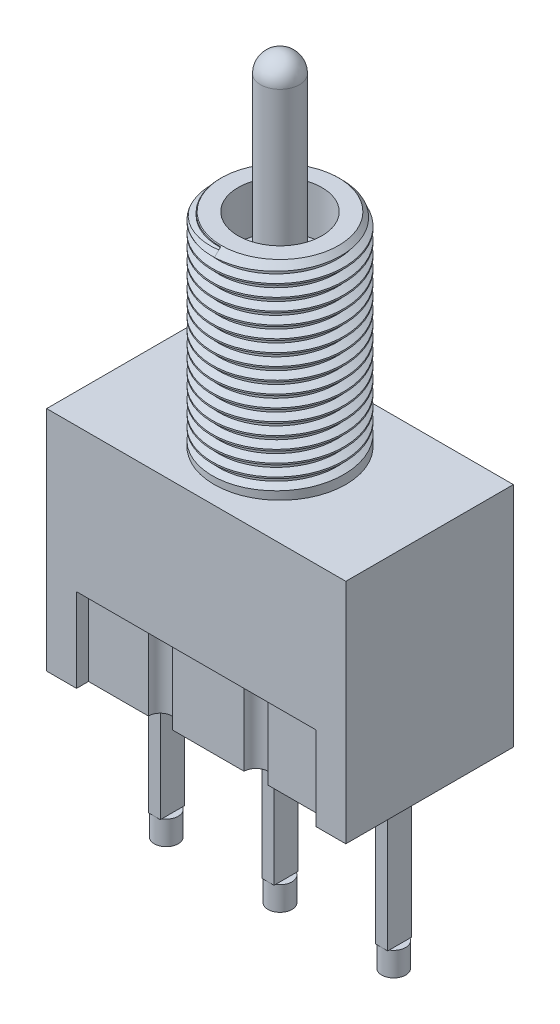
SolidWorks part; units mm, degrees
ref_plane "Front" through (0, 0, 0) normal (0, 0, 1) x (1, 0, 0)
ref_plane "Top" through (0, 0, 0) normal (0, 1, 0) x (1, 0, 0)
ref_plane "Right" through (0, 0, 0) normal (1, 0, 0) x (0, 0, -1)
sketch "Sketch1" plane through (0, 0, 0) normal (0, 1, 0) x (1, 0, 0)
  line L0 (0, 0.4087) -> (0, 3.9087) construction
  line L1 (0, 0.4087) -> (6.25, 0.4087) construction
  line L3 (-6.25, 3.9087) -> (6.25, 3.9087)
  line L4 (-6.25, 3.9087) -> (-6.25, -3.0913)
  line L5 (-6.25, -3.0913) -> (6.25, -3.0913)
  line L6 (6.25, 3.9087) -> (6.25, -3.0913)
  dimension "D1" = 12.5
  dimension "D2" = 7
extrude "Boss-Extrude1" add sketch "Sketch1" along normal blind 9.5
sketch "Sketch2" plane through (0, 0, 0) normal (0, -1, 0) x (1, 0, 0)
  line L0 (0, 3.0913) -> (0, -3.9087) construction
  line L1 (-6.25, 3.0913) -> (6.25, 3.0913) construction
  line L2 (-5, 3.0913) -> (5, 3.0913)
  line L3 (-5, 3.0913) -> (-5, 2.5913)
  line L4 (-5, 2.5913) -> (-2.5, 2.5913)
  line L5 (5, 3.0913) -> (5, 2.5913)
  line L6 (-6.25, -0.4087) -> (6.25, -0.4087) construction
  line L7 (-5, -3.9087) -> (5, -3.9087)
  line L8 (-5, -3.9087) -> (-5, -3.4087)
  line L9 (5, -3.9087) -> (5, -3.4087)
  line L10 (-5, -3.4087) -> (-2.5, -3.4087)
  line L11 (-2, -3.4087) -> (-2, 2.5913) construction
  line L12 (-1.5, -3.4087) -> (1.5, -3.4087)
  line L13 (-1.5, 2.5913) -> (1.5, 2.5913)
  line L14 (2.5, 2.5913) -> (5, 2.5913)
  line L15 (2.5, -3.4087) -> (5, -3.4087)
  arc A0 (-1.5, -3.4087) -> (-2.5, -3.4087) centre (-2, -3.4087) ccw
  arc A1 (-1.5, 2.5913) -> (-2.5, 2.5913) centre (-2, 2.5913) cw
  arc A2 (1.5, 2.5913) -> (2.5, 2.5913) centre (2, 2.5913) ccw
  arc A3 (1.5, -3.4087) -> (2.5, -3.4087) centre (2, -3.4087) cw
  dimension "D4" = 0.5
  dimension "D1" = 5
  dimension "D2" = 5
  dimension "D3" = 0.5
  dimension "D5" = 2
extrude "Cut-Extrude1" cut sketch "Sketch2" against normal blind 3.5
sketch "Sketch3" plane through (0, 0, 0) normal (0, -1, 0) x (1, 0, 0)
  line L0 (-6.25, -0.4087) -> (6.25, -0.4087) construction
  line L2 (6.25, 3.0913) -> (6.25, -3.9087) construction
  line L3 (0, -3.4087) -> (0, 2.5913) construction
  line L5 (-1.5, 2.5913) -> (1.5, 2.5913) construction
  line L6 (1.5, -3.4087) -> (-1.5, -3.4087) construction
  line L7 (-2.5, 1.0913) -> (-1.5, 1.0913)
  line L8 (-2.5, 1.0913) -> (-2.5, -1.9087)
  line L9 (-2.5, -1.9087) -> (-1.5, -1.9087)
  line L10 (-1.5, 1.0913) -> (-1.5, -1.9087)
  line L11 (-6.25, -3.9087) -> (-6.25, 3.0913) construction
  line L12 (2.5, -1.9087) -> (1.5, -1.9087)
  line L13 (1.5, 1.0913) -> (1.5, -1.9087)
  line L14 (2.5, 1.0913) -> (1.5, 1.0913)
  line L15 (2.5, 1.0913) -> (2.5, -1.9087)
  point P13 (6.25, -0.4087)
  point P17 (-6.25, -0.4087)
  point P18 (-2.5, -0.4087)
  point P19 (0, 2.5913)
  point P22 (0, -3.4087)
  dimension "D1" = 1
  dimension "D2" = 1.5
  dimension "D3" = 3
extrude "Boss-Extrude2" add sketch "Sketch3" along normal blind 1
sketch "Sketch4" plane through (0, 0, 0) normal (0, -1, 0) x (1, 0, 0)
  line L0 (-6.25, -0.4087) -> (6.25, -0.4087) construction
  line L1 (-6.25, -3.9087) -> (-6.25, 3.0913) construction
  line L2 (6.25, 3.0913) -> (6.25, -3.9087) construction
  line L5 (-1.5, 2.5913) -> (1.5, 2.5913) construction
  line L7 (0, 2.5913) -> (0, -3.4087) construction
  line L8 (-5, 0.0913) -> (-4.5, 0.0913)
  line L9 (-5, 0.0913) -> (-5, -0.9087)
  line L10 (-5, -0.9087) -> (-4.5, -0.9087)
  line L11 (-4.5, 0.0913) -> (-4.5, -0.9087)
  line L12 (4.5, 0.0913) -> (4.5, -0.9087)
  line L13 (-0.25, 0.0913) -> (0.25, 0.0913)
  line L14 (-0.25, 0.0913) -> (-0.25, -0.9087)
  line L15 (-0.25, -0.9087) -> (0.25, -0.9087)
  line L16 (0.25, 0.0913) -> (0.25, -0.9087)
  line L17 (5, -0.9087) -> (4.5, -0.9087)
  line L18 (5, 0.0913) -> (4.5, 0.0913)
  line L19 (5, 0.0913) -> (5, -0.9087)
  line L21 (1.5, -3.4087) -> (-1.5, -3.4087) construction
  point P4 (-6.25, -0.4087)
  point P7 (6.25, -0.4087)
  point P28 (0, 2.5913)
  point P31 (0, -3.4087)
  dimension "D1" = 0.5
  dimension "D2" = 0.5
  dimension "D3" = 0.5
  dimension "D4" = 1.25
  dimension "D5" = 0.5
  dimension "D6" = 0.5
  dimension "D7" = 0.5
  dimension "D8" = 6
extrude "Boss-Extrude3" add sketch "Sketch4" along normal blind 6
sketch "Sketch5" plane through (0, 9.5, 0) normal (0, 1, 0) x (1, 0, 0)
  line L2 (6.25, 3.9087) -> (-6.25, 3.9087) construction
  line L5 (-6.25, 3.9087) -> (-6.25, -3.0913) construction
  circle A0 centre (0, 0.4087) radius 2.75
  dimension "D1" = 5.5
  dimension "D2" = 3.5
  dimension "D3" = 6.25
extrude "Boss-Extrude4" add sketch "Sketch5" along normal blind 8.5
sketch "Sketch6" plane through (0, 18, 0) normal (0, 1, 0) x (1, 0, 0)
  circle A1 centre (0, 0.4087) radius 2.4795
  dimension "D1" = 4.959
curve "Helix/Spiral1" pitch 0.5 height 8.125 radius 2.4795 centre (0, 18, -0.4087) axis (0, -1, 0) start towards (0, 0, 1)
sketch "Sketch8" plane through (0, 0, 0) normal (1, 0, 0) x (0, 0, -1)
  line L0 (-2.0708, 16) -> (-2.0708, 19.2271) construction
  line L1 (-2.0708, 18) -> (-3.0145, 18) construction
  line L2 (-2.0708, 17.5) -> (-3.0145, 17.5) construction
  line L3 (-2.0708, 17.5) -> (-1.4984, 17.5) construction
  line L4 (-1.4984, 18.5) -> (-2.9633, 18.5) construction
  line L5 (-2.0708, 18) -> (-1.4984, 18) construction
  line L6 (-2.3415, 18.7523) -> (-2.3415, 16.8073) construction
  line L7 (-2.0708, 18.0625) -> (-2.3415, 18.2187)
  line L8 (-2.0708, 17.9375) -> (-2.3415, 17.7813)
  line L9 (-2.0708, 18.0625) -> (-2.0708, 17.9375)
  line L10 (-2.0708, 18.0625) -> (-1.9626, 18) construction
  line L11 (-1.9626, 18) -> (-2.0708, 17.9375) construction
  line L12 (-2.3415, 18.2187) -> (-2.5919, 18.2187)
  line L13 (-2.5919, 18.2187) -> (-2.5919, 17.7813)
  line L14 (-2.5919, 17.7813) -> (-2.3415, 17.7813)
  point P14 (-2.0708, 18.0625)
  point P16 (-2.0708, 17.9375)
  dimension "D1" = 0.5
  dimension "D2" = 0.2706
  dimension "D3" = 0.5
  dimension "D4" = 60
  dimension "D5" = 30
  dimension "D6" = 0.1083
chamfer "Chamfer1" distance 0.3 angle 45 1 edges at (0, 18, 2.3413)
sweep "Cut-Sweep2" cut profiles "Sketch8" path "Helix/Spiral1"
sketch "Sketch9" plane through (0, 0, -0.4087) normal (0, 0, 1) x (1, 0, 0)
  line L0 (-2.7501, 10.0937) -> (-2.7501, 9.6563) construction
  line L1 (-2.7501, 10.0937) -> (-2.4795, 9.9375) construction
  line L2 (-2.4795, 9.9375) -> (-2.4795, 9.8125) construction
  line L3 (-2.4795, 9.8125) -> (-2.7501, 9.6563) construction
  line L4 (-2.7501, 10.0937) -> (-2.7501, 9.6563)
  line L5 (-2.7501, 10.0937) -> (-2.4795, 9.9375)
  line L6 (-2.4795, 9.9375) -> (-2.4795, 9.8125)
  line L7 (-2.4795, 9.8125) -> (-2.7501, 9.6563)
extrude "Cut-Extrude2" cut sketch "Sketch9" against normal blind 2.8
sketch "Sketch11" plane through (0, 18, 0) normal (0, 1, 0) x (1, 0, 0)
  circle A0 centre (0, 0.4087) radius 1.75
  dimension "D1" = 3.5
extrude "Cut-Extrude3" cut sketch "Sketch11" against normal blind 2 contours A0
sketch "Sketch12" plane through (0, 0, 0) normal (0, 0, 1) x (1, 0, 0)
  line L0 (0, 17.7) -> (0, 9.5) construction
  point P0 (0, 16.1983)
ref_plane "Plane1" through (0, 0, 0) normal (-1, 0, 0) x (0, 0, 1)
sketch "Sketch13" plane through (0, 0, 0) normal (-1, 0, 0) x (0, 0, 1)
  line L0 (0, 16.1983) -> (-0.4201, 16.1983) construction
ref_axis "Axis1" through (0, 16.1983, 0) along (0, 0, -1)
sketch "Sketch14" plane through (0, 18, 0) normal (0, 1, 0) x (1, 0, 0)
  line L0 (0, 0.4087) -> (2.75, 0.4087) construction
  line L2 (2.75, -0.0913) -> (2.25, -0.0913)
  line L3 (2.75, -0.0913) -> (2.75, 0.9087)
  line L4 (2.75, 0.9087) -> (2.25, 0.9087)
  line L5 (2.25, -0.0913) -> (2.25, 0.9087)
  line L6 (2.75, -0.0913) -> (2.25, 0.9087) construction
  line L7 (2.75, 0.9087) -> (2.25, -0.0913) construction
  point P2 (3.2835, 0.4087)
  dimension "D2" = 0.5
  dimension "D3" = 1
  dimension "D4" = 0.5
  dimension "D5" = 2.75
sketch "Sketch15" plane through (0, -6, 0) normal (0, -1, 0) x (1, 0, 0)
  circle A0 centre (0, -0.4087) radius 0.5
  circle A1 centre (4.75, -0.4087) radius 0.5
  circle A2 centre (-4.75, -0.4087) radius 0.5
extrude "Boss-Extrude5" add sketch "Sketch15" along normal blind 1
sketch "Sketch16" plane through (0, 16, 0) normal (0, 1, 0) x (1, 0, 0)
  circle A1 centre (0, 0.4087) radius 0.8144
extrude "Boss-Extrude6" add sketch "Sketch16" along normal blind 7
sketch "Sketch17" plane through (0, 23, 0) normal (0, 1, 0) x (1, 0, 0)
  line L0 (-0.8144, 0.4087) -> (0.8144, 0.4087)
  circle A1 centre (0, 0.4087) radius 0.8144
  arc A2 (-0.8144, 0.4087) -> (0.8144, 0.4087) centre (0, 0.4087) ccw
  dimension "D1" = 0
revolve "Revolve1" add sketch "Sketch17" angle 360 about L0
